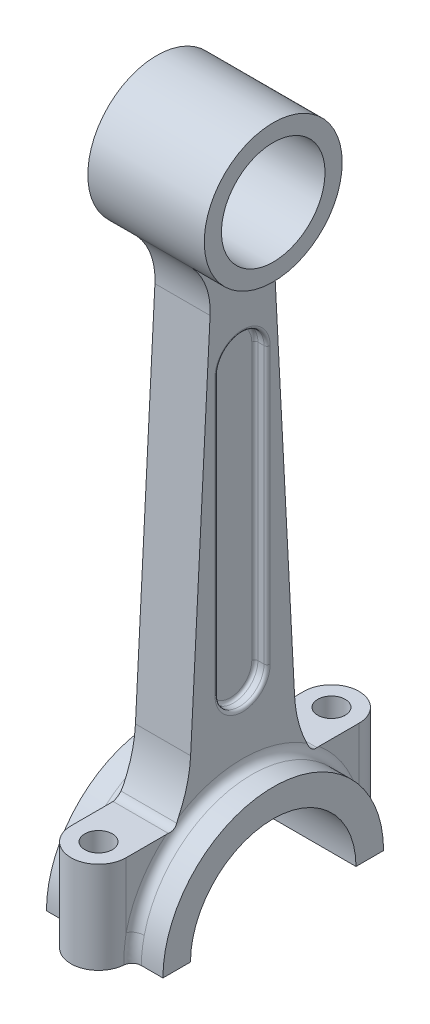
SolidWorks part; units mm, degrees
ref_plane "Front Plane" through (0, 0, 0) normal (0, 0, 1) x (1, 0, 0)
ref_plane "Top Plane" through (0, 0, 0) normal (0, 1, 0) x (1, 0, 0)
ref_plane "Right Plane" through (0, 0, 0) normal (1, 0, 0) x (0, 0, -1)
sketch "Sketch1" plane through (0, 0, 0) normal (1, 0, 0) x (0, 0, -1)
  line L0 (-466.9026, 0) -> (22878.226, 0) construction
  line L1 (0, -466.9026) -> (0, 22878.226) construction
  line L2 (10, -20.1556) -> (16.9576, -152.9141)
  line L3 (-10, -20.1556) -> (-16.9576, -152.9141)
  line L4 (-47, -201.2) -> (47, -201.2)
  line L5 (47, -201.2) -> (47, -171.2)
  line L6 (47, -171.2) -> (19.8997, -171.2)
  line L7 (-47, -171.2) -> (-19.8997, -171.2)
  line L8 (-47, -201.2) -> (-47, -171.2)
  line L9 (0, -50) -> (0, -140) construction
  line L10 (8, -50) -> (8, -140)
  line L11 (-8, -50) -> (-8, -140)
  circle A0 centre (0, 0) radius 16.9
  circle A1 centre (0, 0) radius 22.5
  arc A2 (27, -201.2) -> (-27, -201.2) centre (0, -201.2) ccw
  arc A3 (36, -201.2) -> (-36, -201.2) centre (0, -201.2) ccw
  arc A4 (16.9576, -152.9141) -> (26.9539, -177.3361) centre (56.9028, -150.8207) ccw
  arc A5 (-16.9576, -152.9141) -> (-26.9539, -177.3361) centre (-56.9028, -150.8207) cw
  arc A6 (8, -50) -> (-8, -50) centre (0, -50) ccw
  arc A7 (-8, -140) -> (8, -140) centre (0, -140) ccw
  point P24 (0, -201.2)
  point P27 (0, -95)
  point P35 (0, 0)
  point P36 (0, 0)
  dimension "D1" = 33.8
  dimension "D2" = 45
  dimension "D3" = 54
  dimension "D4" = 72
  dimension "D7" = 40
  dimension "D12" = 8
  dimension "D5" = 201.2
  dimension "D6" = 20
  dimension "D8" = 6
  dimension "D9" = 94
  dimension "D10" = 30
  dimension "D11" = 90
  dimension "D13" = 50
extrude "Boss-Extrude2" add sketch "Sketch1" along normal mid plane 38 contours L4 A3 A2 | A1 A0 region at (0, -21.8636, 0) region at (0, -174.6454, -23.0986)
extrude "Boss-Extrude3" add sketch "Sketch1<4>" along normal mid plane 18 contours L6 A4 A3 L4 L5 | A4 L6 A3 | A5 L7 L8 L4 A3 | L7 A5 A3 region at (0, -172.7087, -22.6888) region at (0, -183.9384, -38.6271) region at (0, -183.9384, 38.6271) region at (0, -172.7087, 22.6888)
sketch "Sketch1<4>" plane through (0, 0, 0) normal (1, 0, 0) x (0, 0, -1) same geometry as "Sketch1"
extrude "Boss-Extrude4" add sketch "Sketch1<5>" along normal mid plane 18 contours L3 A5 L7 A3 L6 A4 L2 A1 A7 L11 A6 L10 region at (0, -86.6174, -11.905)
sketch "Sketch1<5>" plane through (0, 0, 0) normal (1, 0, 0) x (0, 0, -1) same geometry as "Sketch1"
extrude "Boss-Extrude5" add sketch "Sketch1<6>" along normal mid plane 10 contours L11 A7 L10 A6 region at (0, -95, 0)
sketch "Sketch1<6>" plane through (0, 0, 0) normal (1, 0, 0) x (0, 0, -1) same geometry as "Sketch1"
fillet "Fillet1" radius 22.5 2 edges at (0, -20.1556, -10) (0, -20.1556, 10)
fillet "Fillet2" radius 1 16 edges at (-9, -95, 8) (-9, -42, 0) (-9, -95, -8) (-5, -95, 8) (-5, -42, 0) (-5, -95, -8) (9, -95, 8) (9, -42, 0) (9, -95, -8) (5, -95, 8) (5, -42, 0) (5, -95, -8) (-9, -148, 0) (-5, -148, 0) (9, -148, 0) (5, -148, 0)
fillet "Fillet3" 2 edges at (9, -186.2, -47) (-9, -186.2, -47) type full round first side face at (9, -95, 0) second side face at (-9, -95, 0) middle face at (0, -186.2, -47)
fillet "Fillet4" 2 edges at (-9, -186.2, 47) (9, -186.2, 47) type full round first side face at (-9, -95, 0) second side face at (9, -95, 0) middle face at (0, -186.2, 47)
hole_wizard "Ø10.0mm Dowel Hole2" positions "Sketch4" profile "Sketch5" hole size "Ø10.0" standard "ANSI Metric" end condition up to next
sketch "Sketch4" plane through (0, -201.2, 0) normal (0, -1, 0) x (-1, 0, 0)
  point P0 (0, 38)
  point P3 (0, -38)
sketch "Sketch5" plane through (0, -201.2, -38) normal (1, 0, 0) x (0, 0, -1)
  line L0 (0, 0) -> (0, 30)
  line L1 (0, 30) -> (4.5, 30)
  line L2 (4.5, 30) -> (4.5, 0.525)
  line L3 (4.5, 0.525) -> (5.025, 0)
  line L5 (5.025, 0) -> (0, 0)
  line L6 (-4.5, 0.525) -> (-5.025, 0) construction
  line L11 (0, -6.35) -> (0, 107.95) construction
  dimension "Thru Hole Dia." = 9
  dimension "Thru Hole Depth" = 30
  dimension "Near C'Sink Dia." = 10.05
  dimension "Near C'Sink Angle" = 90
fillet "Fillet5" radius 3 2 edges at (-9, -165.2, 0) (9, -165.2, 0)
fillet "Fillet6" radius 3 2 edges at (0, -171.2, -22.4835) (0, -171.2, 22.4835)
